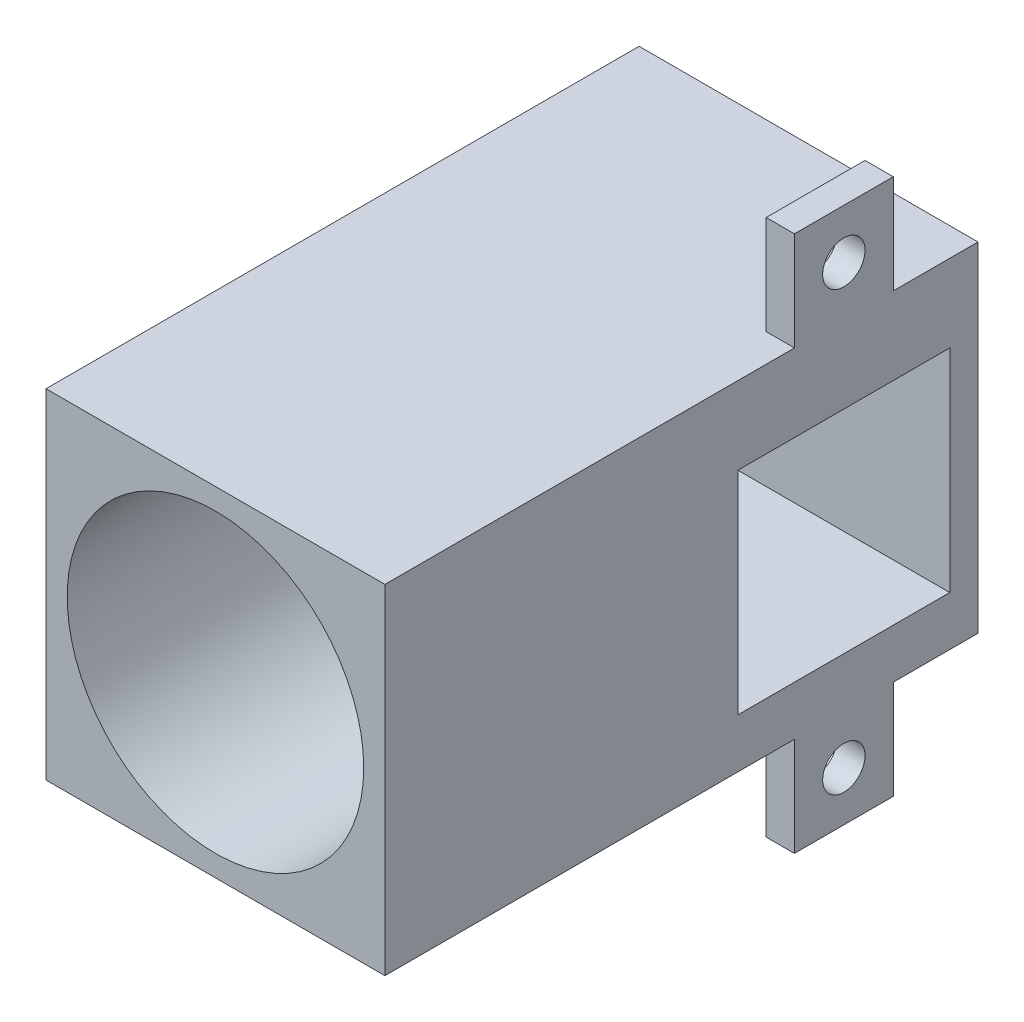
SolidWorks part; units mm, degrees
ref_plane "Спереди" through (0, 0, 0) normal (0, 0, 1) x (1, 0, 0)
ref_plane "Сверху" through (0, 0, 0) normal (0, 1, 0) x (1, 0, 0)
ref_plane "Справа" through (0, 0, 0) normal (1, 0, 0) x (0, 0, -1)
sketch "Эскиз1" plane through (0, 0, 0) normal (0, 0, 1) x (1, 0, 0)
  line L1 (12, 12) -> (-12, 12)
  line L2 (-12, 12) -> (-12, -12)
  line L3 (-12, -12) -> (12, -12)
  line L4 (12, -12) -> (12, 12)
  point P0 (12.2931, 12)
extrude "Бобышка-Вытянуть1" add sketch "Эскиз1" along normal blind 42
sketch "Эскиз3" plane through (0, 0, 42) normal (0, 0, 1) x (1, 0, 0)
  circle A0 centre (0, 0) radius 10.5
extrude "Вырез-Вытянуть1" cut sketch "Эскиз3" against normal blind 20
sketch "Эскиз4" plane through (0, 0, 22) normal (0, 0, 1) x (1, 0, 0)
  line L1 (8.5, 8.5) -> (-8.5, 8.5)
  line L2 (8.5, 8.5) -> (8.5, -8.5)
  line L3 (8.5, -8.5) -> (-8.5, -8.5)
  line L4 (-8.5, 8.5) -> (-8.5, -8.5)
  line L5 (8.5, 8.5) -> (-8.5, -8.5) construction
  line L6 (8.5, -8.5) -> (-8.5, 8.5) construction
  point P0 (0, 0)
extrude "Вырез-Вытянуть2" cut sketch "Эскиз4" against normal blind 20
sketch "Эскиз5" plane through (12, 0, 0) normal (1, 0, 0) x (0, 0, -1)
  line L1 (-2, -8.5) -> (-17, -8.5)
  line L7 (-2, 0) -> (-2, -8.5)
  line L8 (-17, -8.5) -> (-17, 6.5)
  line L9 (-17, 6.5) -> (-2, 6.5)
  line L10 (-2, 6.5) -> (-2, 0)
extrude "Вырез-Вытянуть5" cut sketch "Эскиз5" against normal through all
sketch "Эскиз6" plane through (12, 0, 0) normal (1, 0, 0) x (0, 0, -1)
  line L2 (-42, 12) -> (0, 12) construction
  line L3 (-6, 12) -> (-13, 12)
  line L5 (-6, 12) -> (-6, 19)
  line L6 (-6, 19) -> (-13, 19)
  line L7 (-13, 19) -> (-13, 12)
  line L12 (-42, -12) -> (0, -12) construction
  line L14 (-13, -12) -> (-13, -19)
  line L15 (-13, -19) -> (-6, -19)
  line L16 (-6, -19) -> (-6, -12)
  line L17 (-6, -12) -> (-13, -12)
  circle A0 centre (-9.5, -15.5) radius 1.5
  circle A1 centre (-9.5, 15.5) radius 1.5
extrude "Бобышка-Вытянуть2" add sketch "Эскиз6" against normal blind 2
